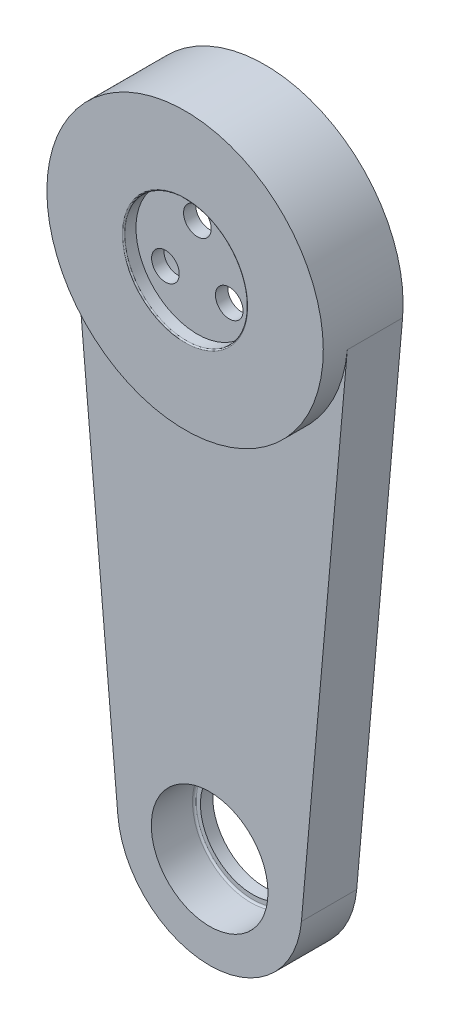
SolidWorks part; units mm, degrees
other "마크업1"
sketch "스케치14" plane through (30, 31, -30.5354) normal (0.2605, 0.9636, -0.0594) x (0.9655, -0.2601, 0.014)
sketch "스케치15" plane through (30, 31, -30.5354) normal (0.2605, 0.9636, -0.0594) x (0.9655, -0.2601, 0.014)
sketch "스케치16" plane through (30, 31, -30.5354) normal (0.2605, 0.9636, -0.0594) x (0.9655, -0.2601, 0.014)
sketch "스케치21" plane through (30, 31, -30.5354) normal (0.2605, 0.9636, -0.0594) x (0.9655, -0.2601, 0.014)
sketch "스케치23" plane through (30, 275, -27) normal (0.2605, 0.9636, -0.0594) x (0.9655, -0.2601, 0.014)
sketch "스케치28" plane through (20, 265, -24) normal (0.2605, 0.9636, -0.0594) x (0.9655, -0.2601, 0.014)
sketch "스케치31" plane through (20, 265, -24) normal (0.2605, 0.9636, -0.0594) x (0.9655, -0.2601, 0.014)
sketch "스케치32" plane through (20, 265, -23) normal (0.2605, 0.9636, -0.0594) x (0.9655, -0.2601, 0.014)
sketch "스케치33" plane through (20, 265, -23) normal (0.2605, 0.9636, -0.0594) x (0.9655, -0.2601, 0.014)
sketch "스케치52" plane through (24, 65, -12) normal (0.2605, 0.9636, -0.0594) x (0.9655, -0.2601, 0.014)
sketch "스케치61" plane through (22.5, 22.5, -13) normal (0.2605, 0.9636, -0.0594) x (0.9655, -0.2601, 0.014)
sketch "스케치64" plane through (22.5, 22.5, -13) normal (0.2605, 0.9636, -0.0594) x (0.9655, -0.2601, 0.014)
sketch "스케치70" plane through (22.5, 22.5, -13) normal (0.2605, 0.9636, -0.0594) x (0.9655, -0.2601, 0.014)
material "7075-T6 (SN)"
ref_plane "정면" through (0, 0, 0) normal (0, 0, 1) x (1, 0, 0)
ref_plane "윗면" through (0, 0, 0) normal (0, 1, 0) x (1, 0, 0)
ref_plane "우측면" through (0, 0, 0) normal (1, 0, 0) x (0, 0, -1)
sketch "스케치2" plane through (0, 6, 0) normal (0, 0, -1) x (1, 0, 0)
  circle A0 centre (0, 6) radius 22.5
  dimension "D1" = 45
extrude "보스-돌출2" add sketch "스케치2" along normal blind 2
sketch "스케치22" plane through (0, 0, 0) normal (0, 0, 1) x (1, 0, 0)
  circle A0 centre (0, 0) radius 10
  dimension "D1" = 20
extrude "컷-돌출1" cut sketch "스케치22" against normal blind 2 contours A0
fillet "필렛4" radius 0.2 1 edges at (10, 0, 0)
sketch "스케치54" plane through (0, 0, -2) normal (0, 0, -1) x (-1, 0, 0)
  circle A4 centre (0, 0) radius 22.5 construction
  circle A5 centre (0, 0) radius 22.5
extrude "보스-돌출6" add sketch "스케치54" along normal blind 11
sketch "스케치55" plane through (0, 0, -13) normal (0, 0, -1) x (-1, 0, 0)
  circle A0 centre (0, 0) radius 18.5
  dimension "D1" = 37
extrude "컷-돌출2" cut sketch "스케치55" against normal blind 8
sketch "스케치56" plane through (0, 0, -5) normal (0, 0, -1) x (-1, 0, 0)
  circle A0 centre (0, 0) radius 6 construction
  point P3 (0, 6)
  dimension "D1" = 12
hole_wizard "M4 육각 소켓 머리 캡 나사용 카운터보어1" positions "스케치57" profile "스케치58" counterbore size "M4" standard "ISO" end condition through all
sketch "스케치57" plane through (0, 0, -5) normal (0, 0, -1) x (-1, 0, 0)
  point P0 (0, 6)
sketch "스케치58" plane through (0, 6, -5) normal (1, 0, 0) x (0, 1, 0)
  line L0 (0, 0) -> (0, 5)
  line L1 (0, 5) -> (2.25, 5)
  line L3 (2.25, 5) -> (2.25, 1)
  line L4 (2.25, 1) -> (4, 1)
  line L5 (4, 1) -> (4, 0)
  line L7 (4, 0) -> (0, 0)
  line L11 (0, -6.35) -> (0, 107.95) construction
  dimension "관통 구멍 지름" = 4.5
  dimension "관통 구멍 깊이" = 5
  dimension "카운터보어 지름" = 8
  dimension "카운터보어 깊이" = 1
pattern_circular "원형 패턴1" count 3 over 360 about axis through (0, 0, -2) along (0, 0, 1) of "M4 육각 소켓 머리 캡 나사용 카운터보어1"
sketch "스케치59" plane through (0, 0, -5) normal (0, 0, -1) x (-1, 0, 0)
  circle A0 centre (0, 0) radius 17.5
  circle A1 centre (0, 0) radius 18.5 construction
  circle A2 centre (0, 0) radius 18.5
  dimension "D1" = 35
extrude "보스-돌출7" add sketch "스케치59" along normal blind 1
sketch "스케치60" plane through (0, 0, -13) normal (0, 0, -1) x (-1, 0, 0)
  line L0 (-22.4122, -1.9853) -> (-14.9415, -86.3235)
  line L1 (0, 0) -> (0, -85) construction
  line L2 (22.4122, -1.9853) -> (14.9415, -86.3235)
  circle A0 centre (0, 0) radius 22.5 construction
  arc A1 (-14.9415, -86.3235) -> (14.9415, -86.3235) centre (0, -85) ccw
  arc A2 (-22.4122, -1.9853) -> (22.4122, -1.9853) centre (0, 0) ccw
  dimension "D2" = 30
  dimension "D1" = 85
extrude "보스-돌출8" add sketch "스케치60" against normal blind 9
fillet "필렛6" radius 0.3 1 edges at (-18.5, 0, -6)
sketch "스케치68" plane through (0, 0, -4) normal (0, 0, 1) x (1, 0, 0)
  circle A0 centre (0, -85) radius 9.5
  dimension "D1" = 19
extrude "컷-돌출7" cut sketch "스케치68" against normal blind 7
sketch "스케치69" plane through (0, 0, -11) normal (0, 0, 1) x (1, 0, 0)
  circle A0 centre (0, -85) radius 8.5
  dimension "D1" = 17
extrude "컷-돌출8" cut sketch "스케치69" against normal through all
fillet "필렛7" radius 0.3 1 edges at (9.5, -85, -11)
